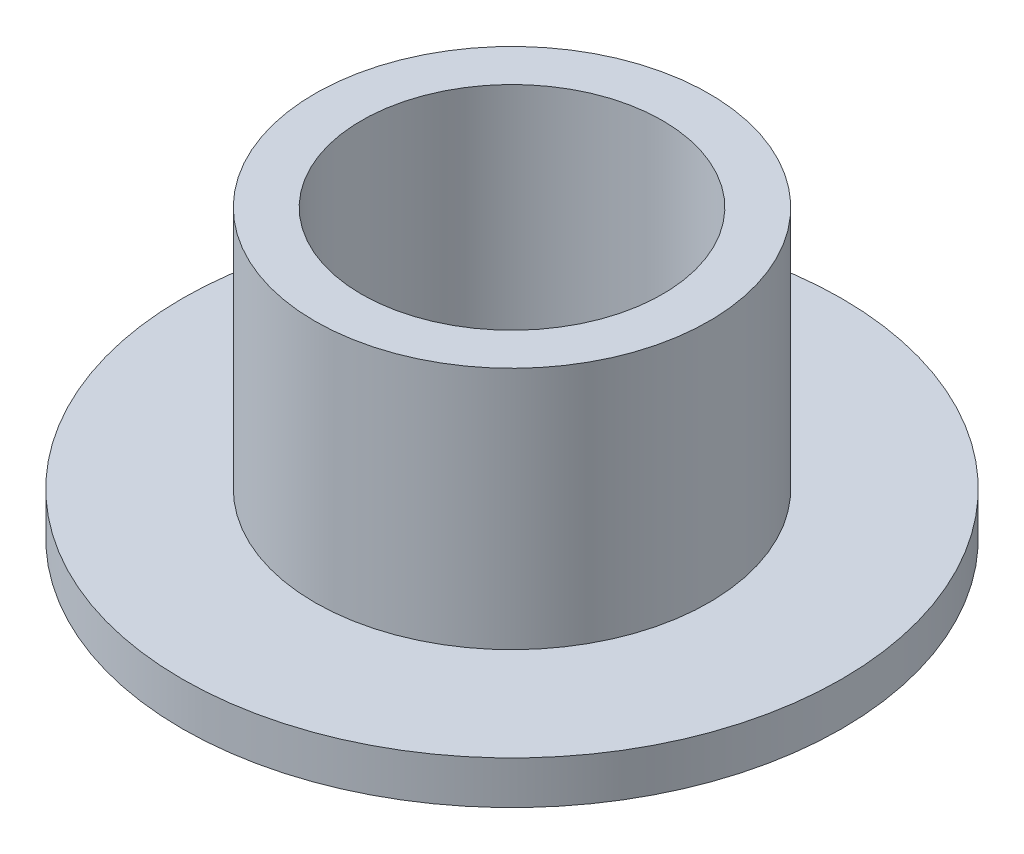
SolidWorks part; units mm, degrees
ref_plane "前视基准面" through (0, 0, 0) normal (0, 0, 1) x (1, 0, 0)
ref_plane "上视基准面" through (0, 0, 0) normal (0, 1, 0) x (1, 0, 0)
ref_plane "右视基准面" through (0, 0, 0) normal (1, 0, 0) x (0, 0, -1)
sketch "草图1" plane through (0, 0, 0) normal (0, 1, 0) x (1, 0, 0)
  circle A0 centre (0, 0) radius 2.75
  circle A1 centre (0, 0) radius 2.1
  circle A2 centre (0, 0) radius 4.6
  dimension "D1" = 4.2
  dimension "D2" = 5.5
  dimension "D3" = 9.2
extrude "凸台-拉伸1" add sketch "草图1" along normal blind 3.4 contours A0 A1 region at (-2.6722, 0, 0)
extrude "凸台-拉伸2" add sketch "草图1<3>" against normal blind 0.6 contours A2 A0 | A0 A1 region at (-2.6722, 0, 0) region at (-4.4699, 0, 0)
sketch "草图1<3>" plane through (0, 0, 0) normal (0, 1, 0) x (1, 0, 0) same geometry as "草图1"
